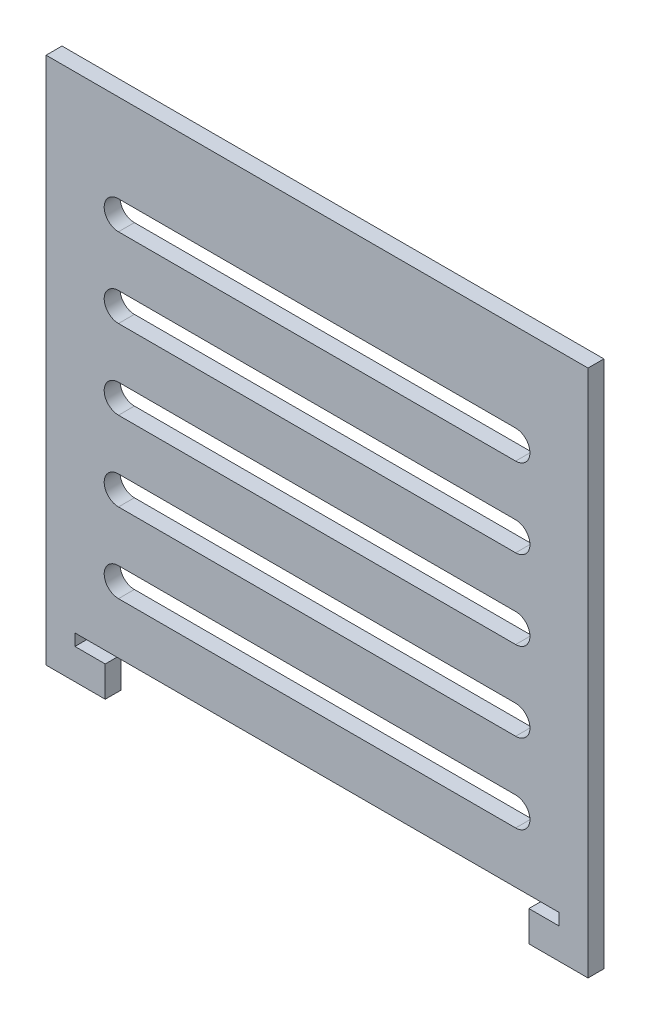
SolidWorks part; units mm, degrees
ref_plane "Front Plane" through (0, 0, 0) normal (0, 0, 1) x (1, 0, 0)
ref_plane "Top Plane" through (0, 0, 0) normal (0, 1, 0) x (1, 0, 0)
ref_plane "Right Plane" through (0, 0, 0) normal (1, 0, 0) x (0, 0, -1)
sketch "Sketch1" plane through (0, 0, 0) normal (0, 0, 1) x (1, 0, 0)
  line L0 (0, 0) -> (0, 9.63)
  line L1 (0, 9.63) -> (-9.53, 9.63)
  line L2 (-9.53, 9.63) -> (-9.53, 13.32)
  line L3 (-9.53, 13.32) -> (142.87, 13.32)
  line L4 (142.87, 13.32) -> (142.87, 9.63)
  line L5 (142.87, 9.63) -> (133.34, 9.63)
  line L6 (133.34, 9.63) -> (133.34, 0)
  line L7 (133.34, 0) -> (151.95, 0)
  line L8 (151.95, 0) -> (151.95, 166.26)
  line L9 (151.95, 166.26) -> (-18.61, 166.26)
  line L10 (-18.61, 166.26) -> (-18.61, 0)
  line L11 (-18.61, 0) -> (0, 0)
  line L12 (4.17, 38.5096) -> (129.17, 38.5096)
  line L13 (4.17, 29.5096) -> (129.17, 29.5096)
  arc A0 (4.17, 38.5096) -> (4.17, 29.5096) centre (4.17, 34.0096) ccw
  arc A1 (129.17, 29.5096) -> (129.17, 38.5096) centre (129.17, 34.0096) ccw
  dimension "D7" = 9
  dimension "D9" = 22.78
  dimension "D1" = 166.26
  dimension "D2" = 170.56
  dimension "D3" = 18.61
  dimension "D4" = 3.69
  dimension "D5" = 9.63
  dimension "D6" = 152.4
  dimension "D8" = 125
  dimension "D10" = 16.1896
extrude "Boss-Extrude1" add sketch "Sketch1" along normal blind 5 contours L13 A1 L12 A0 | L10 L11 L0 L1 L2 L3 L4 L5 L6 L7 L8 L9 region at (66.67, 34.0096, 0)
pattern_linear "LPattern1" count 5 spacing 25 along (0, 1, 0) of face at (66.67, 38.5096, 2.5) of face at (1.92, 34.0096, 2.5) of face at (131.42, 34.0096, 2.5) of face at (66.67, 29.5096, 2.5)
